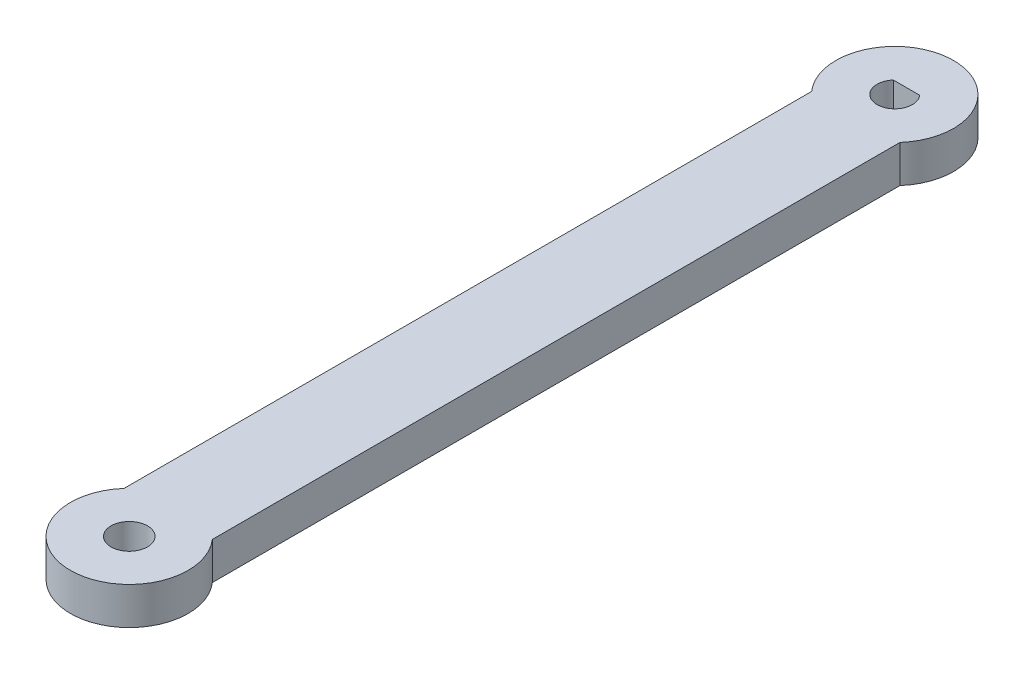
SolidWorks part; units mm, degrees
ref_plane "Front Plane" through (0, 0, 0) normal (0, 0, 1) x (1, 0, 0)
ref_plane "Top Plane" through (0, 0, 0) normal (0, 1, 0) x (1, 0, 0)
ref_plane "Right Plane" through (0, 0, 0) normal (1, 0, 0) x (0, 0, -1)
sketch "Sketch1" plane through (0, 0, 0) normal (0, 1, 0) x (1, 0, 0)
  line L0 (-1.118, 1) -> (1.118, 1)
  line L1 (-3.75, -61.6928) -> (-3.75, -3.3072)
  line L4 (3.75, -61.6928) -> (3.75, -3.3072)
  line L5 (-3.75, -3.3072) -> (0, 0) construction
  line L6 (0, 0) -> (3.75, -3.3072) construction
  line L7 (-3.75, -3.3072) -> (3.75, -3.3072) construction
  line L8 (-1.118, 1) -> (0, 0) construction
  line L9 (0, 0) -> (1.118, 1) construction
  arc A1 (3.75, -3.3072) -> (-3.75, -3.3072) centre (0, 0) ccw
  arc A2 (-3.75, -61.6928) -> (3.75, -61.6928) centre (0, -65) ccw
  circle A3 centre (0, -65) radius 1.55
  arc A4 (-1.118, 1) -> (1.118, 1) centre (0, 0) ccw
  point P5 (-7.4251, 3.5103)
  dimension "D3" = 10
  dimension "D6" = 10
  dimension "D5" = 3.1
  dimension "D8" = 3
  dimension "D1" = 2.2361
  dimension "D4" = 7.5
  dimension "D7" = 65
extrude "Boss-Extrude1" add sketch "Sketch1" along normal blind 3.175
